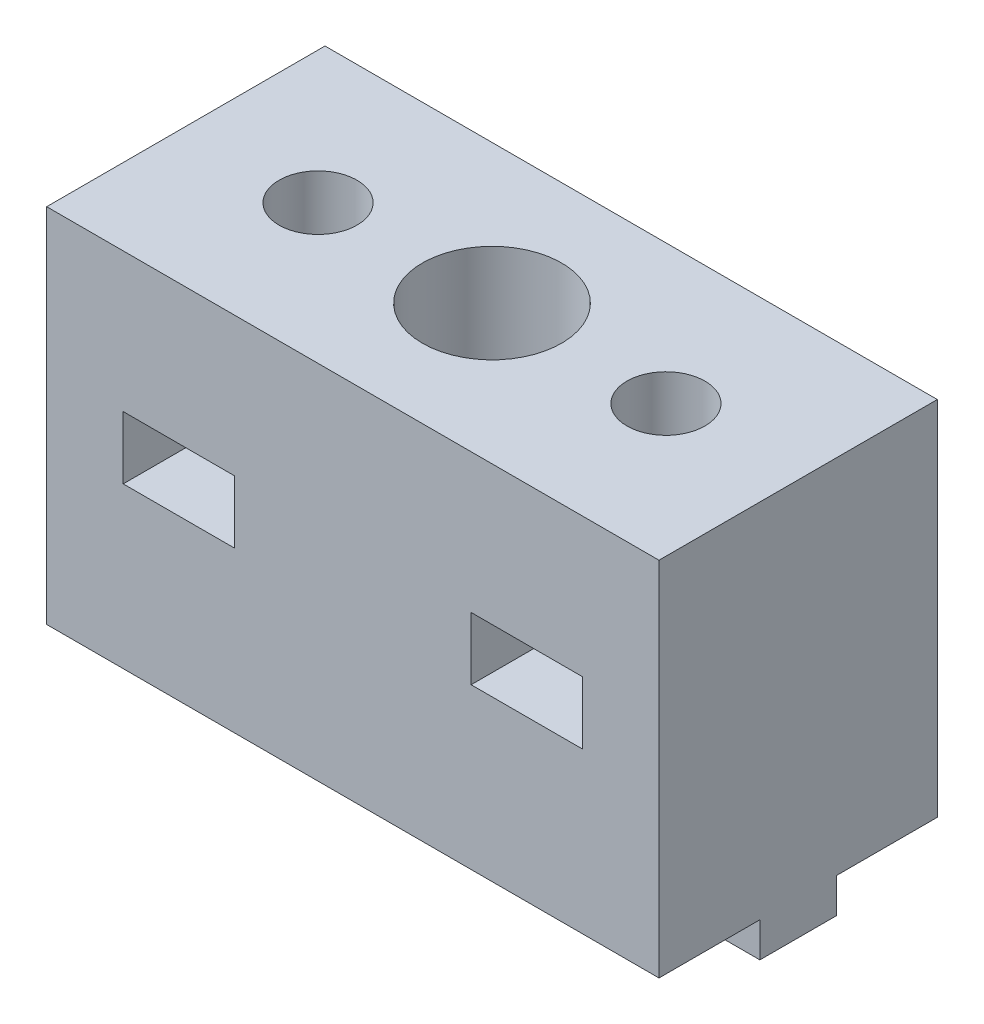
SolidWorks part; units mm, degrees
ref_plane "Front Plane" through (0, 0, 0) normal (0, 0, 1) x (1, 0, 0)
ref_plane "Top Plane" through (0, 0, 0) normal (0, 1, 0) x (1, 0, 0)
ref_plane "Right Plane" through (0, 0, 0) normal (1, 0, 0) x (0, 0, -1)
sketch "Sketch1" plane through (0, 0, 0) normal (0, 1, 0) x (1, 0, 0)
  line L1 (-0.6968, 0) -> (43.3032, 0)
  line L2 (-0.6968, 0) -> (-0.6968, 20)
  line L3 (-0.6968, 20) -> (43.3032, 20)
  line L4 (43.3032, 0) -> (43.3032, 20)
  dimension "D1" = 20
  dimension "D2" = 44
extrude "Boss-Extrude1" add sketch "Sketch1" along normal blind 26
sketch "Sketch3" plane through (0, 0, 0) normal (0, -1, 0) x (1, 0, 0)
  line L0 (43.3032, 0) -> (43.3032, -20) construction
  line L1 (43.3032, -12.75) -> (-0.6968, -12.75)
  line L2 (43.3032, -12.75) -> (43.3032, -7.25)
  line L3 (43.3032, -7.25) -> (-0.6968, -7.25)
  line L4 (-0.6968, -12.75) -> (-0.6968, -7.25)
  line L5 (-0.6968, -20) -> (-0.6968, 0) construction
  line L6 (43.3032, -20) -> (-0.6968, -20) construction
  dimension "D1" = 5.5
  dimension "D2" = 7.25
extrude "Boss-Extrude5" add sketch "Sketch3" along normal blind 2.5
sketch "Sketch2" plane through (0, 26, 0) normal (0, 1, 0) x (1, 0, 0)
  line L0 (43.3032, 20) -> (-0.6968, 20) construction
  line L1 (-0.6968, 20) -> (-0.6968, 0) construction
  line L2 (43.3032, 0) -> (43.3032, 20) construction
  circle A0 centre (8.8032, 10) radius 2.8
  circle A1 centre (33.8032, 10) radius 2.8
  circle A2 centre (21.3032, 10) radius 2.8
  dimension "D1" = 5.6
  dimension "D2" = 5.6
  dimension "D3" = 5.6
  dimension "D4" = 22
  dimension "D5" = 10
  dimension "D6" = 10
  dimension "D7" = 25
  dimension "D9" = 9.5
extrude "Cut-Extrude1" cut sketch "Sketch2" against normal through all
sketch "Sketch4" plane through (0, 26, 0) normal (0, 1, 0) x (1, 0, 0)
  line L0 (-0.6968, 0) -> (43.3032, 0) construction
  line L1 (-0.6968, 20) -> (-0.6968, 0) construction
  circle A0 centre (21.3032, 10) radius 5
  dimension "D1" = 10
  dimension "D2" = 10
  dimension "D3" = 22
extrude "Cut-Extrude2" cut sketch "Sketch4" against normal offset from surface (21 mm away) 5 up to face at (21.3032, 0, -5.785)
sketch "Sketch5" plane through (0, 0, -20) normal (0, 0, -1) x (-1, 0, 0)
  line L1 (-37.8032, 11.5) -> (-29.8032, 11.5)
  line L2 (-37.8032, 11.5) -> (-37.8032, 16)
  line L3 (-37.8032, 16) -> (-29.8032, 16)
  line L4 (-29.8032, 11.5) -> (-29.8032, 16)
  line L5 (-12.8032, 11.5) -> (-4.8032, 11.5)
  line L6 (-12.8032, 11.5) -> (-12.8032, 16)
  line L7 (-12.8032, 16) -> (-4.8032, 16)
  line L8 (-4.8032, 11.5) -> (-4.8032, 16)
  line L9 (-43.3032, 26) -> (0.6968, 26) construction
  line L10 (-43.3032, 26) -> (-43.3032, 0) construction
  line L11 (0.6968, 26) -> (0.6968, 0) construction
  dimension "D1" = 4.5
  dimension "D2" = 8
  dimension "D3" = 4.5
  dimension "D4" = 8
  dimension "D5" = 10
  dimension "D6" = 10
  dimension "D7" = 5.5
  dimension "D8" = 5.5
extrude "Cut-Extrude3" cut sketch "Sketch5" against normal through all
